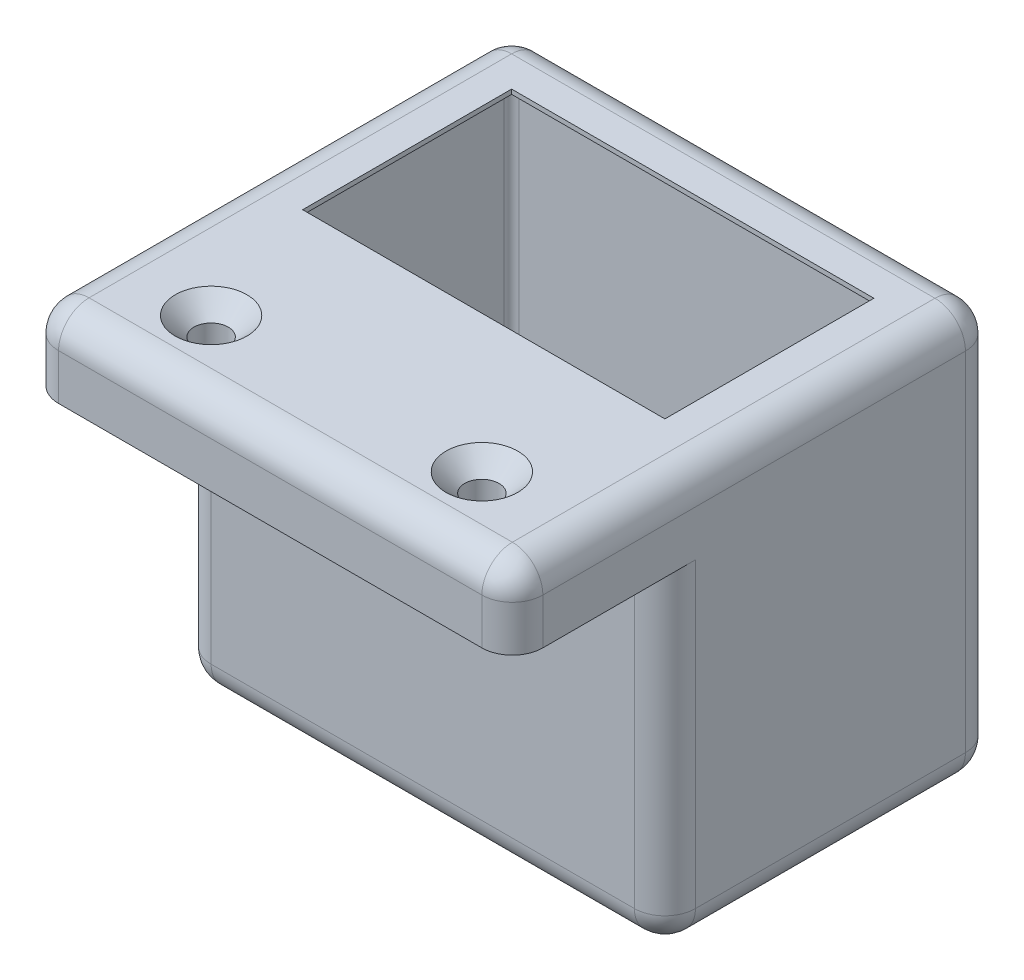
SolidWorks part; units mm, degrees
ref_plane "Front Plane" through (0, 0, 0) normal (0, 0, 1) x (1, 0, 0)
ref_plane "Top Plane" through (0, 0, 0) normal (0, 1, 0) x (1, 0, 0)
ref_plane "Right Plane" through (0, 0, 0) normal (1, 0, 0) x (0, 0, -1)
sketch "Profile Sketch" plane through (0, 0, 0) normal (1, 0, 0) x (0, 0, -1)
  line L0 (0, 0) -> (0, 43.6)
  line L1 (0, 43.6) -> (-20, 43.6)
  line L2 (-20, 43.6) -> (-20, 53.6)
  line L3 (-20, 53.6) -> (43.4, 53.6)
  line L4 (43.4, 53.6) -> (43.4, 0)
  line L5 (43.4, 0) -> (0, 0)
  dimension "D1" = 63.4
  dimension "D2" = 10
  dimension "D3" = 43.4
  dimension "D4" = 53.6
extrude "Profile Extrude" add sketch "Profile Sketch" along normal mid plane 63.5
sketch "Interior Sketch" plane through (0, 0, 0) normal (0, -1, 0) x (1, 0, 0)
  line L8 (-28.75, -3) -> (-28.75, -40.4)
  line L9 (-28.75, -40.4) -> (28.75, -40.4)
  line L10 (28.75, -40.4) -> (28.75, -3)
  line L11 (28.75, -3) -> (-28.75, -3)
  line L12 (-28.75, -3) -> (-28.75, -40.4)
  line L13 (-28.75, -40.4) -> (28.75, -40.4)
  line L14 (28.75, -40.4) -> (28.75, -3)
  line L15 (28.75, -3) -> (-28.75, -3)
  dimension "D1" = 3
extrude "Interior Cut" cut sketch "Interior Sketch" against normal offset from surface (50 mm away) 0.6 from offset 3 up to face at (0, 53.6, -11.7) offset against normal yes
sketch "Opening Sketch" plane through (0, 53.6, 0) normal (0, 1, 0) x (1, 0, 0)
  line L8 (-23.75, 8) -> (23.75, 8)
  line L9 (-23.75, 35.4) -> (-23.75, 8)
  line L10 (23.75, 35.4) -> (-23.75, 35.4)
  line L11 (23.75, 8) -> (23.75, 35.4)
  line L12 (-23.75, 8) -> (23.75, 8)
  line L13 (-23.75, 35.4) -> (-23.75, 8)
  line L14 (23.75, 35.4) -> (-23.75, 35.4)
  line L15 (23.75, 8) -> (23.75, 35.4)
  dimension "D1" = 5
extrude "Opening Cut" cut sketch "Opening Sketch" against normal up to next
chamfer "Inside Top Chamfer" distance 5 angle 45 4 edges at (28.75, 53, -21.7) (0, 53, -40.4) (-28.75, 53, -21.7) (0, 53, -3)
fillet "Inside Fillets" radius 1 4 edges at (-28.75, 25.5, -3) (28.75, 25.5, -3) (28.75, 25.5, -40.4) (-28.75, 25.5, -40.4)
sketch "Wire Outlet Cut Sketch" plane through (0, 0, 0) normal (0, -1, 0) x (1, 0, 0)
  line L0 (-31.75, -43.4) -> (31.75, 0) construction
  circle A0 centre (0, -21.7) radius 9.5
  dimension "D1" = 19
extrude "Wire Outlet Cut" cut sketch "Wire Outlet Cut Sketch" against normal up to next
fillet "Wire Outlet Fillet" 2 edges at (0, 0, -31.2) (0, 3, -31.2) type full round first side face at (0, 0, -31.2) second side face at (0, 3, -31.2) middle face at (0, 0, -31.2)
fillet "Top Fillets" radius 4 14 edges at (0, 0, 0) (31.75, 0, -21.7) (0, 0, -43.4) (-31.75, 0, -21.7) (-31.75, 26.8, -43.4) (0, 53.6, -43.4) (31.75, 26.8, -43.4) (-31.75, 21.8, 0) (31.75, 21.8, 0) (-31.75, 53.6, -11.7) (-31.75, 48.6, 20) (0, 53.6, 20) (31.75, 53.6, -11.7) (31.75, 48.6, 20)
sketch "Mounting Hole Layout Sketch" plane through (0, 53.6, 0) normal (0, 1, 0) x (1, 0, 0)
  line L0 (0, 0) -> (0, -27.8287) construction
  line L1 (27.75, -20) -> (-27.75, -20) construction
  point P3 (-17.75, -10)
  point P4 (17.75, -10)
  dimension "D1" = 35.5
  dimension "D2" = 10
hole_wizard "M4 Mounting Screws" positions "M4 Mounting Screws Position Sketch" profile "M4 Mounting Screws Profile Sketch" countersink size "M4" standard "ANSI Metric" end condition up to next
sketch3d "M4 Mounting Screws Position Sketch"
  point P0 (-17.75, 53.6, 10)
  point P3 (17.75, 53.6, 10)
sketch "M4 Mounting Screws Profile Sketch" plane through (-17.75, 53.6, 10) normal (1, 0, 0) x (0, 0, 1)
  line L0 (0, 0) -> (0, 10)
  line L1 (0, 10) -> (2.25, 10)
  line L2 (2.25, 10) -> (2.25, 2.45)
  line L3 (2.25, 2.45) -> (4.7, 0)
  line L5 (4.7, 0) -> (0, 0)
  line L6 (-2.25, 2.45) -> (-4.7, 0) construction
  line L11 (0, -6.35) -> (0, 107.95) construction
  dimension "Thru Hole Dia." = 4.5
  dimension "Thru Hole Depth" = 10
  dimension "Near C'Sink Dia." = 9.4
  dimension "Near C'Sink Angle" = 90
